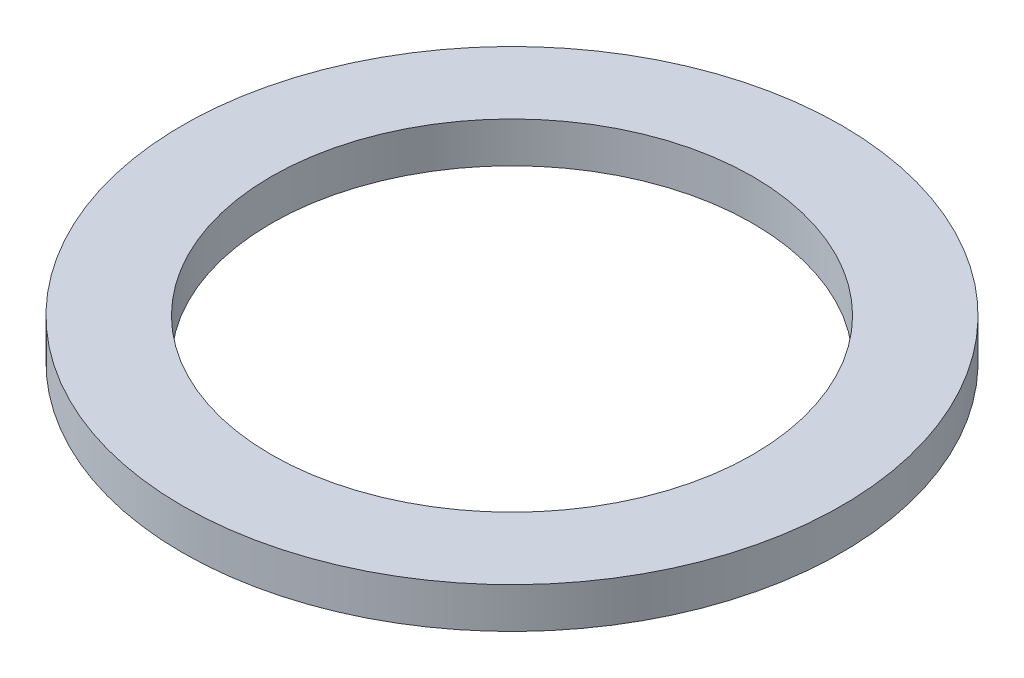
SolidWorks part; units mm, degrees
ref_plane "Front Plane" through (0, 0, 0) normal (0, 0, 1) x (1, 0, 0)
ref_plane "Top Plane" through (0, 0, 0) normal (0, 1, 0) x (1, 0, 0)
ref_plane "Right Plane" through (0, 0, 0) normal (1, 0, 0) x (0, 0, -1)
sketch "Sketch1" plane through (0, 0, 0) normal (0, 1, 0) x (1, 0, 0)
  circle A0 centre (0, 0) radius 65
  dimension "FLANGE_OD" = 130
extrude "Boss-Extrude1" add sketch "Sketch1" along normal blind 8
sketch "Sketch2" plane through (0, 0, 0) normal (0, 1, 0) x (1, 0, 0)
  circle A0 centre (0, 0) radius 47.5
  dimension "BORE_D" = 95
extrude "Cut-Extrude1" cut sketch "Sketch2" along normal through all
sketch "Sketch3" plane through (0, 8, 0) normal (0, 1, 0) x (1, 0, 0)
  circle A0 centre (0, 0) radius 27.7939 construction
  circle A1 centre (-27.7939, 0) radius 1.8847
  dimension "BOLT_D" = 3.7695
  dimension "BOLT_PCD" = 55.5879
extrude "Cut-Extrude2" cut sketch "Sketch3" against normal blind 7.1955 rebuild error yes
pattern_circular "CirPattern1" count 8 over 360 rebuild error yes
